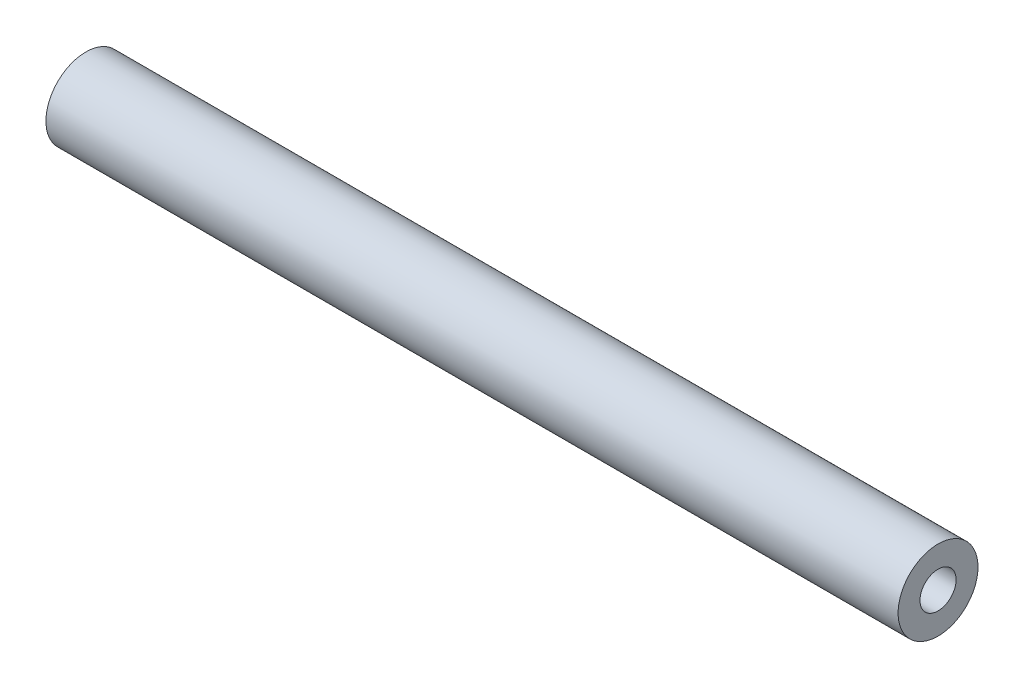
SolidWorks part; units mm, degrees
ref_plane "Front Plane" through (0, 0, 0) normal (0, 0, 1) x (1, 0, 0)
ref_plane "Top Plane" through (0, 0, 0) normal (0, 1, 0) x (1, 0, 0)
ref_plane "Right Plane" through (0, 0, 0) normal (1, 0, 0) x (0, 0, -1)
sketch "Sketch1" plane through (0, 0, 0) normal (1, 0, 0) x (0, 0, -1)
  circle A0 centre (0, 0) radius 4.7625
  circle A1 centre (0, 0) radius 2.1526
  dimension "D1" = 9.525
  dimension "D2" = 4.3053
extrude "Boss-Extrude1" add sketch "Sketch1" along normal blind 101.6
